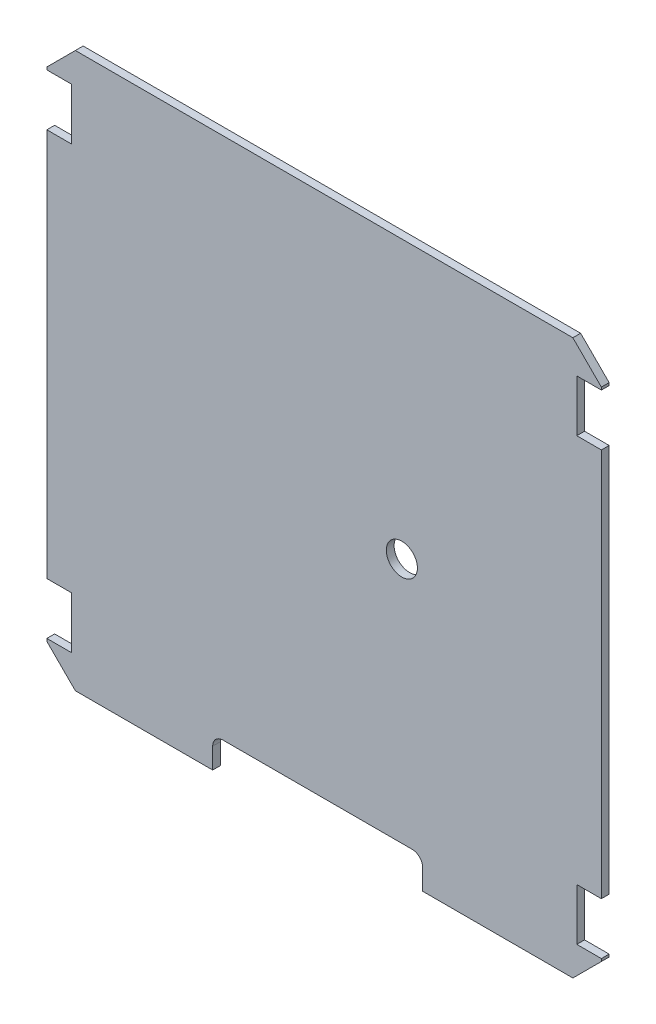
SolidWorks part; units mm, degrees
material "1060 Alloy"
ref_plane "Front Plane" through (0, 0, 0) normal (0, 0, 1) x (1, 0, 0)
ref_plane "Top Plane" through (0, 0, 0) normal (0, 1, 0) x (1, 0, 0)
ref_plane "Right Plane" through (0, 0, 0) normal (1, 0, 0) x (0, 0, -1)
sketch "Sketch1" plane through (0, 0, 0) normal (0, 0, 1) x (1, 0, 0)
  line L0 (-100, -100) -> (100, -100) construction
  line L1 (-100, -100) -> (-100, 100) construction
  line L2 (100, -100) -> (100, 100) construction
  line L3 (-100, 100) -> (100, 100) construction
  line L4 (-100, -100) -> (100, 100) construction
  line L5 (100, -100) -> (-100, 100) construction
  line L6 (-107, 0) -> (107, 0) construction
  line L7 (-107, -107) -> (107, -107)
  line L8 (-107, -107) -> (-107, 107)
  line L9 (-107, 107) -> (107, 107)
  line L10 (107, -107) -> (107, 107)
  line L11 (-107, -107) -> (107, 107) construction
  line L12 (-107, 107) -> (107, -107) construction
  circle A0 centre (-104.5, 104.5) radius 1.6 construction
  circle A1 centre (104.5, 104.5) radius 1.6 construction
  circle A2 centre (0, -104.5) radius 1.6
  circle A3 centre (104.5, -104.5) radius 1.6 construction
  circle A4 centre (-104.5, -104.5) radius 1.6 construction
  point P0 (0, 0)
  point P1 (0, 0)
  dimension "D4" = 3.2
  dimension "D1" = 209
  dimension "D2" = 200
  dimension "D3" = 214
  dimension "D5" = 209
extrude "Boss-Extrude1" add sketch "Sketch1" along normal blind 3
sketch "Sketch2" plane through (0, 0, 3) normal (0, 0, 1) x (1, 0, 0)
  line L0 (-107, -107) -> (107, -107) construction
  line L1 (-43, -107) -> (38, -107)
  line L2 (-43, -107) -> (-43, -95)
  line L3 (-43, -95) -> (38, -95)
  line L4 (38, -107) -> (38, -95)
  line L5 (-107, 107) -> (-107, -107) construction
  line L6 (-107, -95) -> (-97.5051, -95)
  line L7 (-107, -95) -> (-107, -75)
  line L8 (-107, -75) -> (-97.5051, -75)
  line L9 (-97.5051, -95) -> (-97.5051, -75)
  line L10 (107, -107) -> (107, 107) construction
  line L11 (-107, 75) -> (-97.5051, 75)
  line L12 (-107, 75) -> (-107, 95)
  line L13 (-107, 95) -> (-97.5051, 95)
  line L14 (-97.5051, 75) -> (-97.5051, 95)
  line L15 (107, 75) -> (97.5051, 75)
  line L16 (107, 75) -> (107, 95)
  line L17 (107, 95) -> (97.5051, 95)
  line L18 (97.5051, 75) -> (97.5051, 95)
  line L19 (-97.5051, -75) -> (97.5051, 75) construction
  line L20 (107, -95) -> (97.5051, -95)
  line L21 (107, -95) -> (107, -75)
  line L22 (107, -75) -> (97.5051, -75)
  line L23 (97.5051, -95) -> (97.5051, -75)
  line L24 (-97.5051, 75) -> (97.5051, -75) construction
  circle A0 centre (30, 0) radius 6
  dimension "D7" = 12
  dimension "D1" = 12
  dimension "D2" = 43
  dimension "D3" = 81
  dimension "D4" = 20
  dimension "D5" = 12
  dimension "D6" = 30
extrude "Cut-Extrude1" cut sketch "Sketch2" against normal through all
fillet "Fillet1" radius 4 2 edges at (38, -95, 1.5) (-43, -95, 1.5)
chamfer "Chamfer1" distance 11 angle 45 4 edges at (107, 107, 1.5) (-107, 107, 1.5) (-107, -107, 1.5) (107, -107, 1.5)
